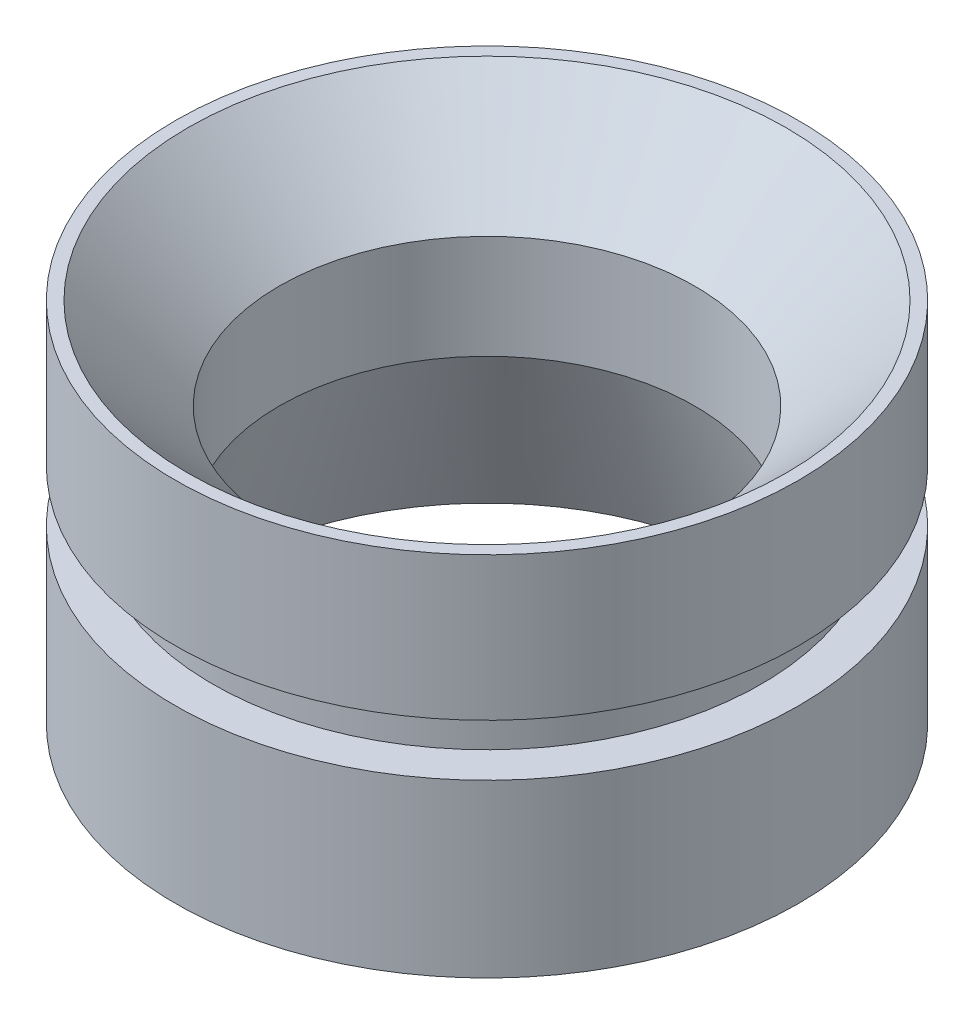
SolidWorks part; units mm, degrees
material "Copper"
ref_plane "Front Plane" through (0, 0, 0) normal (0, 0, 1) x (1, 0, 0)
ref_plane "Top Plane" through (0, 0, 0) normal (0, 1, 0) x (1, 0, 0)
ref_plane "Right Plane" through (0, 0, 0) normal (1, 0, 0) x (0, 0, -1)
sketch "Sketch1" plane through (0, 0, 0) normal (0, 0, 1) x (1, 0, 0)
  line L0 (0, 44.7791) -> (0, -23.856) construction
  line L1 (12.7, -3.175) -> (12.7, 3.175)
  line L2 (12.7, 3.175) -> (18.288, 8.763)
  line L3 (18.288, 8.763) -> (19.05, 8.763)
  line L4 (19.05, 8.763) -> (19.05, 0)
  line L5 (19.05, -13.6429) -> (16.51, -13.6429)
  line L6 (16.51, -13.6429) -> (12.7, -3.175)
  line L7 (19.05, -3.175) -> (19.05, -13.6429)
  line L8 (19.05, 0) -> (16.764, 0)
  line L10 (19.05, -3.175) -> (16.764, -3.175)
  line L12 (16.764, 0) -> (16.764, -3.175)
  point P11 (12.7, 0)
  dimension "D1" = 25.4
  dimension "D2" = 6.35
  dimension "D3" = 45
  dimension "D4" = 20
  dimension "D5" = 0.762
  dimension "D6" = 2.54
  dimension "D7" = 38.1
  dimension "D8" = 3.175
  dimension "D9" = 2.286
revolve "Revolve1" add sketch "Sketch1" angle 360 about L0
fillet "Fillet2" [suppressed] radius 1.524
fillet "Fillet3" [suppressed] radius 0.762
